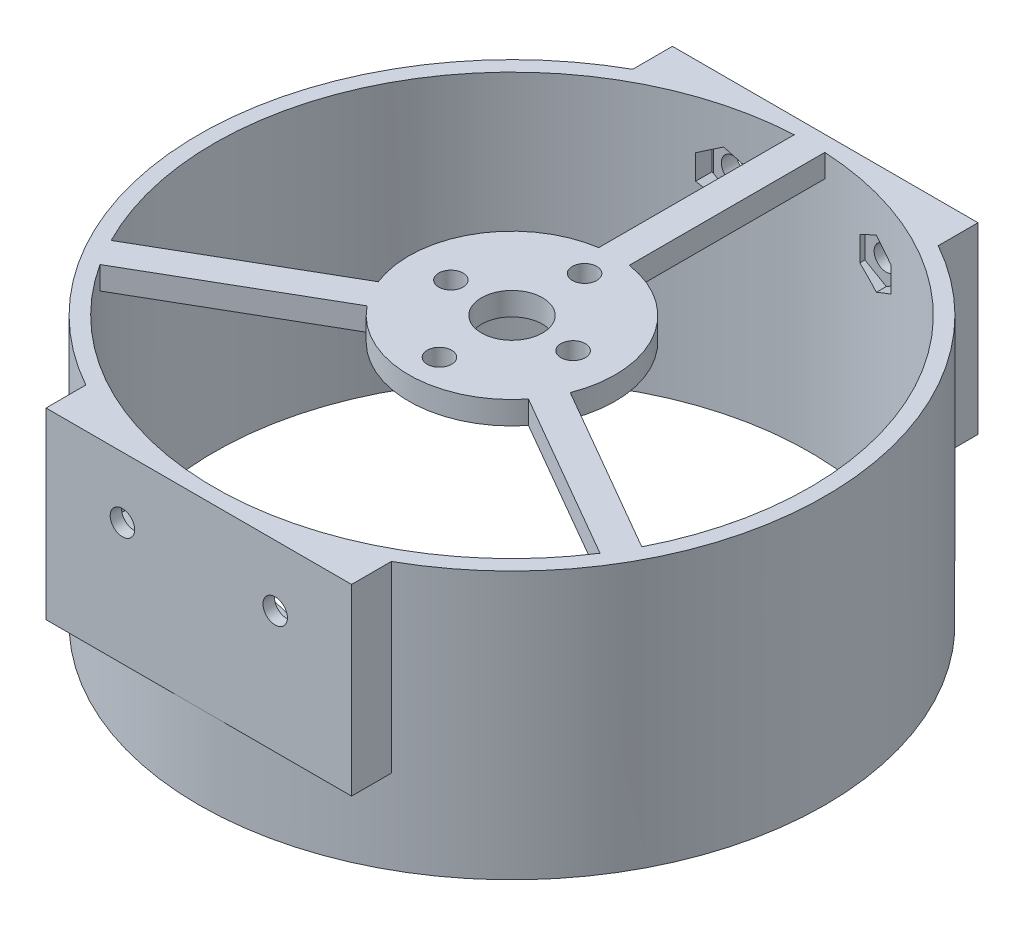
SolidWorks part; units mm, degrees
ref_plane "前视基准面" through (0, 0, 0) normal (0, 0, 1) x (1, 0, 0)
ref_plane "上视基准面" through (0, 0, 0) normal (0, 1, 0) x (1, 0, 0)
ref_plane "右视基准面" through (0, 0, 0) normal (1, 0, 0) x (0, 0, -1)
sketch "草图1" plane through (0, 0, 0) normal (0, 1, 0) x (1, 0, 0)
  circle A0 centre (0, 0) radius 39
  circle A1 centre (0, 0) radius 41
  dimension "D1" = 78
  dimension "D2" = 2
extrude "凸台-拉伸1" add sketch "草图1" along normal blind 20
sketch "草图2" plane through (0, 20, 0) normal (0, 1, 0) x (1, 0, 0)
  line L0 (20, -41) -> (-20, -41)
  line L1 (-20, -41) -> (-20, -35.7911)
  line L2 (0, -41) -> (0, -31.4417) construction
  line L3 (20, -41) -> (20, -35.7911)
  line L4 (0, 0) -> (26.2566, 0) construction
  line L5 (20, 41) -> (20, 35.7911)
  line L6 (20, 41) -> (-20, 41)
  line L7 (-20, 41) -> (-20, 35.7911)
  circle A0 centre (0, 0) radius 41 construction
  arc A1 (-20, -35.7911) -> (20, -35.7911) centre (0, 0) ccw
  arc A2 (-20, 35.7911) -> (20, 35.7911) centre (0, 0) cw
  circle M5 centre (0, 0) radius 41
extrude "凸台-拉伸2" add sketch "草图2" against normal blind 14 contours L1 L0 M5 | L0 L3 M5 region at (15.0657, 20, 39.4559) region at (-15.0657, 20, 39.4559)
sketch "草图3" plane through (0, 20, 0) normal (0, 1, 0) x (1, 0, 0)
  line L0 (-2, 38.9487) -> (-2, 13.351)
  line L1 (0, 39) -> (0, 13.5) construction
  line L2 (2, 38.9487) -> (2, 13.351)
  line L3 (34.7305, -17.7423) -> (12.5623, -4.9435)
  line L4 (32.7305, -21.2064) -> (10.5623, -8.4076)
  line L5 (-32.7305, -21.2064) -> (-10.5623, -8.4076)
  line L6 (-34.7305, -17.7423) -> (-12.5623, -4.9435)
  circle A0 centre (0, 0) radius 4
  circle A1 centre (-8, 0) radius 1.6
  circle A2 centre (8, 0) radius 1.6
  arc A3 (-10.5623, -8.4076) -> (10.5623, -8.4076) centre (0, 0) ccw
  circle A4 centre (0, 0) radius 39 construction
  arc A5 (2, 38.9487) -> (-2, 38.9487) centre (0, 0) ccw
  arc A6 (32.7305, -21.2064) -> (34.7305, -17.7423) centre (0, 0) ccw
  arc A7 (-34.7305, -17.7423) -> (-32.7305, -21.2064) centre (0, 0) ccw
  arc A8 (-2, 13.351) -> (-12.5623, -4.9435) centre (0, 0) ccw
  arc A9 (12.5623, -4.9435) -> (2, 13.351) centre (0, 0) ccw
  point P28 (0, 0)
  dimension "D1" = 8
  dimension "D2" = 3.2
  dimension "D3" = 8
  dimension "D4" = 3.2
  dimension "D5" = 8
  dimension "D6" = 27
  dimension "D7" = 2
  dimension "D8" = 3
extrude "凸台-拉伸3" add sketch "草图3" against normal blind 3
sketch "草图4" plane through (0, 0, 41) normal (0, 0, 1) x (1, 0, 0)
  line L0 (20, 20) -> (-20, 20) construction
  line L1 (-10, 8.7668) -> (-7.2, 10.3834)
  line L2 (-7.2, 10.3834) -> (-7.2, 13.6166)
  line L3 (-7.2, 13.6166) -> (-10, 15.2332)
  line L4 (-10, 15.2332) -> (-12.8, 13.6166)
  line L5 (-12.8, 13.6166) -> (-12.8, 10.3834)
  line L6 (-12.8, 10.3834) -> (-10, 8.7668)
  line L7 (0, 0) -> (0, -4.0742) construction
  line L8 (12.8, 10.3834) -> (10, 8.7668)
  line L9 (12.8, 13.6166) -> (12.8, 10.3834)
  line L10 (10, 15.2332) -> (12.8, 13.6166)
  line L11 (7.2, 13.6166) -> (10, 15.2332)
  line L12 (7.2, 10.3834) -> (7.2, 13.6166)
  line L13 (10, 8.7668) -> (7.2, 10.3834)
  circle A0 centre (-10, 12) radius 2.8 construction
  dimension "D1" = 5.6
  dimension "D2" = 10
  dimension "D3" = 8
sketch "草图7" plane through (0, 6, 0) normal (0, -1, 0) x (1, 0, 0)
  line L2 (-20, 41) -> (-20, 35.7911)
  line L3 (0, 41) -> (-20, 41)
  line L4 (-20, 41) -> (-20, 35.7911)
  line L5 (0, 41) -> (-20, 41)
  line L6 (20, 41) -> (0, 41)
  line L7 (20, 35.7911) -> (20, 41)
  line L8 (20, 41) -> (0, 41)
  line L9 (20, 35.7911) -> (20, 41)
  arc A1 (0, 41) -> (-20, 35.7911) centre (0, 0) ccw
  arc A2 (0, 41) -> (-20, 35.7911) centre (0, 0) ccw
  arc A3 (20, 35.7911) -> (0, 41) centre (0, 0) ccw
  arc A4 (20, 35.7911) -> (0, 41) centre (0, 0) ccw
  line M7 (-20, 41) -> (-20, 35.7911)
  arc M8 (-20, 35.7911) -> (0, 41) centre (0, 0) cw
  line M9 (0, 41) -> (-20, 41)
  dimension "D1" = 0
  dimension "D2" = 0
extrude "切除-拉伸3" cut sketch "草图7" against normal blind 3 contours M9 M7 M8 | A4 L9 L8 region at (-15.0657, 6, 39.4559) region at (15.0657, 6, 39.4559)
sketch "草图9" plane through (0, 0, 0) normal (0, -1, 0) x (1, 0, 0)
sketch "草图10" plane through (0, 0, 0) normal (0, -1, 0) x (1, 0, 0)
sketch "草图11" plane through (0, 0, 0) normal (0, -1, 0) x (1, 0, 0)
sketch "草图12" plane through (0, 0, 0) normal (0, -1, 0) x (1, 0, 0)
  circle A2 centre (0.1979, 0.0085) radius 41.1981
extrude "凸台-拉伸5" add sketch "草图1<2>" along normal blind 10 and the other way blind 15
sketch "草图1<2>" plane through (0, 0, 0) normal (0, 1, 0) x (1, 0, 0) same geometry as "草图1"
extrude "凸台-拉伸7" add sketch "草图7<4>" along normal blind 10
sketch "草图7<4>" plane through (0, 6, 0) normal (0, -1, 0) x (1, 0, 0) same geometry as "草图7"
extrude "凸台-拉伸8" add sketch "草图7<5>" along normal blind 10 and the other way blind 5 contours M9 M7 M8 | A4 L9 L8 region at (-15.0657, 6, 39.4559) region at (15.0657, 6, 39.4559)
sketch "草图7<5>" plane through (0, 6, 0) normal (0, -1, 0) x (1, 0, 0) same geometry as "草图7"
extrude "切除-拉伸4" cut sketch "草图4" against normal blind 80
sketch "草图20" plane through (0, 20, 0) normal (0, 1, 0) x (1, 0, 0)
  line L0 (-20, 35.7911) -> (-20, 41)
  line L1 (-20, 41) -> (20, 41)
  line L2 (20, 41) -> (20, 35.7911)
  arc A0 (-20, 35.7911) -> (20, 35.7911) centre (0, 0) cw
  arc M13 (20, -35.7911) -> (-20, -35.7911) centre (0, 0) ccw
extrude "凸台-拉伸10" add sketch "草图20" against normal blind 24 contours L2 L1 M13 | L1 L0 M13 | L1 L2 A0 L0 region at (15.0657, 20, -39.4559) region at (-15.0657, 20, -39.4559)
extrude "凸台-拉伸9" add sketch "草图4<3>" along normal blind 10 and the other way blind 1.5
sketch "草图4<3>" plane through (0, 0, 41) normal (0, 0, 1) x (1, 0, 0) same geometry as "草图4"
sketch "草图13" plane through (0, 0, 51) normal (0, 0, 1) x (1, 0, 0)
  line L0 (10, 15.2332) -> (7.2, 13.6166)
  line L1 (7.2, 13.6166) -> (7.2, 10.3834)
  line L2 (7.2, 10.3834) -> (10, 8.7668)
  line L3 (10, 8.7668) -> (12.8, 10.3834)
  line L4 (12.8, 10.3834) -> (12.8, 13.6166)
  line L5 (12.8, 13.6166) -> (10, 15.2332)
  line L6 (-10, 15.2332) -> (-12.8, 13.6166)
  line L7 (-12.8, 13.6166) -> (-12.8, 10.3834)
  line L8 (-12.8, 10.3834) -> (-10, 8.7668)
  line L9 (-10, 8.7668) -> (-7.2, 10.3834)
  line L10 (-7.2, 10.3834) -> (-7.2, 13.6166)
  line L11 (-7.2, 13.6166) -> (-10, 15.2332)
extrude "切除-拉伸6" cut sketch "草图13" against normal blind 10
sketch "草图16" plane through (0, 0, 41) normal (0, 0, 1) x (1, 0, 0)
  line L1 (0, 0) -> (0, 20) construction
  line L2 (20, 20) -> (-20, 20) construction
  line L3 (20, 20) -> (-20, 20) construction
  circle A0 centre (-10, 12) radius 1.6
  circle A1 centre (10, 12) radius 1.6
  dimension "D1" = 20
  dimension "D2" = 10
  dimension "D3" = 8
extrude "切除-拉伸7" cut sketch "草图16" against normal blind 103
sketch "草图18" plane through (0, 20, 0) normal (0, 1, 0) x (1, 0, 0)
  circle A1 centre (0, 9.5) radius 1.6
  circle A2 centre (0, -9.5) radius 1.6
  point P2 (0, 0)
  point P3 (0, 0)
extrude "切除-拉伸8" cut sketch "草图18" against normal blind 10 contours A1
extrude "切除-拉伸9" cut sketch "草图18<4>" against normal blind 10
sketch "草图18<4>" plane through (0, 20, 0) normal (0, 1, 0) x (1, 0, 0) same geometry as "草图18"
